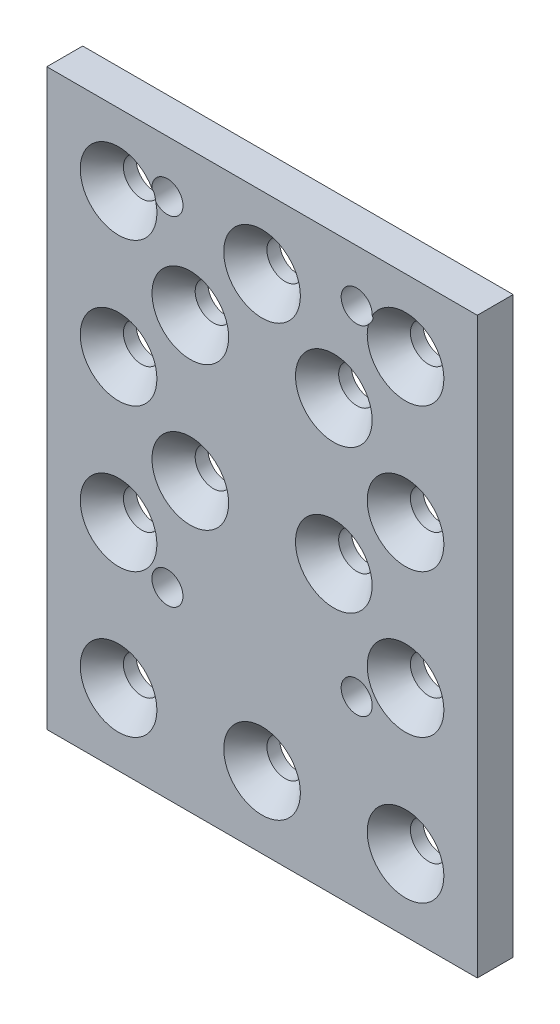
SolidWorks part; units mm, degrees
ref_plane "Front Plane" through (0, 0, 0) normal (0, 0, 1) x (1, 0, 0)
ref_plane "Top Plane" through (0, 0, 0) normal (0, 1, 0) x (1, 0, 0)
ref_plane "Right Plane" through (0, 0, 0) normal (1, 0, 0) x (0, 0, -1)
sketch "Sketch1" plane through (0, 0, 0) normal (0, 0, 1) x (1, 0, 0)
  line L5 (-64.52, -20.9042) -> (11.68, -20.9042)
  line L6 (11.68, -20.9042) -> (11.68, 80.6958)
  line L7 (11.68, 80.6958) -> (-64.52, 80.6958)
  line L8 (-64.52, 80.6958) -> (-64.52, -20.9042)
  line L9 (-64.52, -20.9042) -> (11.68, -20.9042)
  line L10 (11.68, -20.9042) -> (11.68, 80.6958)
  line L11 (11.68, 80.6958) -> (-64.52, 80.6958)
  line L12 (-64.52, 80.6958) -> (-64.52, -20.9042)
  circle A0 centre (-1.02, 17.1958) radius 3.229
  circle A1 centre (-13.72, 29.8958) radius 3.229
  circle A3 centre (-1.02, 42.5958) radius 3.229
  circle A5 centre (-13.72, 55.2958) radius 3.229
  circle A7 centre (-1.02, 67.9958) radius 3.229
  circle A9 centre (-1.02, 17.1958) radius 3.429
  circle A10 centre (-1.02, 17.1958) radius 3.429 construction
  circle A11 centre (-13.72, 29.8958) radius 3.429
  circle A12 centre (-13.72, 29.8958) radius 3.429 construction
  circle A13 centre (-1.02, 42.5958) radius 3.429
  circle A14 centre (-1.02, 42.5958) radius 3.429 construction
  circle A15 centre (-13.72, 55.2958) radius 3.429
  circle A16 centre (-13.72, 55.2958) radius 3.429 construction
  circle A17 centre (-1.02, 67.9958) radius 3.429
  circle A18 centre (-1.02, 67.9958) radius 3.429 construction
  circle A19 centre (-26.42, 67.9958) radius 3.429
  circle A20 centre (-26.42, 67.9958) radius 3.429 construction
  circle A21 centre (-39.12, 55.2958) radius 3.429
  circle A22 centre (-39.12, 55.2958) radius 3.429 construction
  circle A23 centre (-51.82, 67.9958) radius 3.429
  circle A24 centre (-51.82, 67.9958) radius 3.429 construction
  circle A25 centre (-51.82, 42.5958) radius 3.429
  circle A26 centre (-51.82, 42.5958) radius 3.429 construction
  circle A27 centre (-51.82, 17.1958) radius 3.429
  circle A28 centre (-51.82, 17.1958) radius 3.429 construction
  circle A29 centre (-39.12, 29.8958) radius 3.429
  circle A30 centre (-39.12, 29.8958) radius 3.429 construction
  circle A31 centre (-39.12, 4.4958) radius 3.429
  circle A32 centre (-39.12, 4.4958) radius 3.429 construction
  circle A33 centre (-13.72, 4.4958) radius 3.429
  circle A34 centre (-13.72, 4.4958) radius 3.429 construction
  circle A35 centre (-1.02, -8.2042) radius 3.429
  circle A36 centre (-1.02, -8.2042) radius 3.429 construction
  circle A37 centre (-26.42, -8.2042) radius 3.429
  circle A38 centre (-26.42, -8.2042) radius 3.429 construction
  circle A39 centre (-51.82, -8.2042) radius 3.429
  circle A40 centre (-51.82, -8.2042) radius 3.429 construction
  circle A41 centre (-26.42, 67.9958) radius 3.229
  circle A42 centre (-39.12, 55.2958) radius 3.229
  circle A43 centre (-51.82, 67.9958) radius 3.229
  circle A44 centre (-51.82, 42.5958) radius 3.229
  circle A45 centre (-51.82, 17.1958) radius 3.229
  circle A46 centre (-39.12, 29.8958) radius 3.229
  circle A47 centre (-39.12, 4.4958) radius 3.229 construction
  circle A48 centre (-13.72, 4.4958) radius 3.229 construction
  circle A49 centre (-1.02, -8.2042) radius 3.229
  circle A50 centre (-26.42, -8.2042) radius 3.229
  circle A51 centre (-51.82, -8.2042) radius 3.229
  circle A52 centre (-43.17, 11.5538) radius 2.75 construction
  circle A53 centre (-9.67, 11.5538) radius 2.75 construction
  circle A54 centre (-9.67, 71.4538) radius 2.75 construction
  circle A55 centre (-43.17, 71.4538) radius 2.75 construction
  circle A56 centre (-43.17, 11.5538) radius 2.75
  circle A57 centre (-9.67, 11.5538) radius 2.75
  circle A58 centre (-9.67, 71.4538) radius 2.75
  circle A59 centre (-43.17, 71.4538) radius 2.75
  dimension "D3" = 0.2
  dimension "D4" = 0
  dimension "D5" = 0
  dimension "D6" = 0
  dimension "D7" = 0
  dimension "D8" = 0
  dimension "D9" = 0
  dimension "D10" = 0
  dimension "D11" = 0
  dimension "D12" = 0
  dimension "D13" = 0
  dimension "D14" = 0
  dimension "D15" = 0
  dimension "D16" = 0
  dimension "D17" = 0
  dimension "D18" = 0
  dimension "D19" = 0
  dimension "D20" = 0
extrude "Boss-Extrude1" add sketch "Sketch1" along normal blind 6.35
chamfer "Chamfer1" distance 4.0894 angle 41 14 edges at (2.209, 67.9958, 6.35) (-23.191, 67.9958, 6.35) (-48.591, 17.1958, 6.35) (-48.591, 42.5958, 6.35) (-48.591, 67.9958, 6.35) (-10.491, 55.2958, 6.35) (-35.891, 55.2958, 6.35) (-35.891, 29.8958, 6.35) (-10.491, 29.8958, 6.35) (2.209, 42.5958, 6.35) (2.209, 17.1958, 6.35) (2.209, -8.2042, 6.35) (-23.191, -8.2042, 6.35) (-48.591, -8.2042, 6.35) first distance on face at (2.209, 67.9958, 6.35) first distance on face at (-23.191, 67.9958, 6.35) first distance on face at (-48.591, 17.1958, 6.35) first distance on face at (-48.591, 42.5958, 6.35) first distance on face at (-48.591, 67.9958, 6.35) first distance on face at (-10.491, 55.2958, 6.35) first distance on face at (-35.891, 55.2958, 6.35) first distance on face at (-35.891, 29.8958, 6.35) first distance on face at (-10.491, 29.8958, 6.35) first distance on face at (2.209, 42.5958, 6.35) first distance on face at (2.209, 17.1958, 6.35) first distance on face at (2.209, -8.2042, 6.35) first distance on face at (-23.191, -8.2042, 6.35) first distance on face at (-48.591, -8.2042, 6.35)
